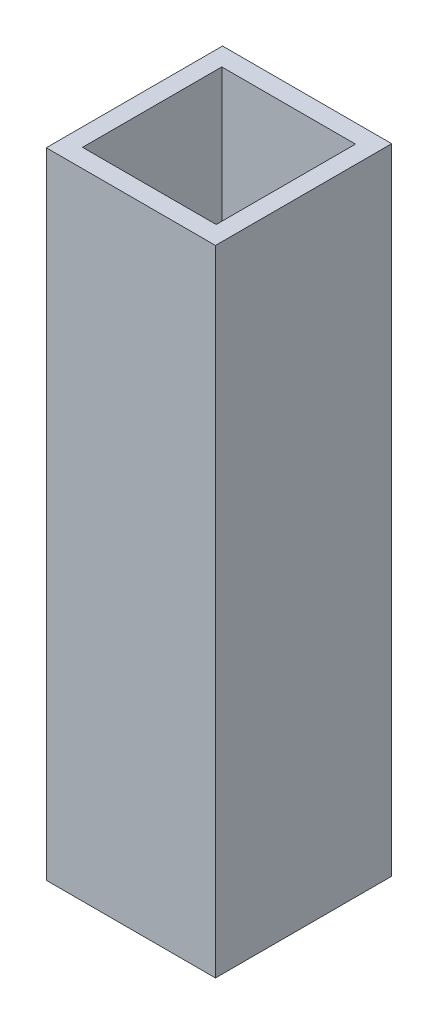
SolidWorks part; units mm, degrees
ref_plane "Front Plane" through (0, 0, 0) normal (0, 0, 1) x (1, 0, 0)
ref_plane "Top Plane" through (0, 0, 0) normal (0, 1, 0) x (1, 0, 0)
ref_plane "Right Plane" through (0, 0, 0) normal (1, 0, 0) x (0, 0, -1)
sketch "Sketch1" plane through (0, 0, 0) normal (0, 1, 0) x (1, 0, 0)
  line L9 (-6, -6.25) -> (6, -6.25)
  line L10 (-6, -6.25) -> (-6, 6.25)
  line L11 (-6, 6.25) -> (6, 6.25)
  line L12 (6, -6.25) -> (6, 6.25)
  line L13 (-6, -6.25) -> (6, 6.25) construction
  line L14 (-6, 6.25) -> (6, -6.25) construction
  line L15 (-4.7416, -4.9392) -> (4.7416, -4.9392)
  line L16 (-4.7416, -4.9392) -> (-4.7416, 4.9392)
  line L17 (-4.7416, 4.9392) -> (4.7416, 4.9392)
  line L18 (4.7416, -4.9392) -> (4.7416, 4.9392)
  line L19 (-4.7416, -4.9392) -> (4.7416, 4.9392) construction
  line L20 (-4.7416, 4.9392) -> (4.7416, -4.9392) construction
  point P0 (0, 0)
  point P6 (0, 0)
  dimension "D1" = 12
  dimension "D2" = 12.5
extrude "Boss-Extrude1" add sketch "Sketch1" along normal blind 45
extrude "Boss-Extrude2" add sketch "Sketch1<2>" along normal blind 2 contours L15 L18 L17 L16 region at (0, 0, 0)
sketch "Sketch1<2>" plane through (0, 0, 0) normal (0, 1, 0) x (1, 0, 0) same geometry as "Sketch1"
